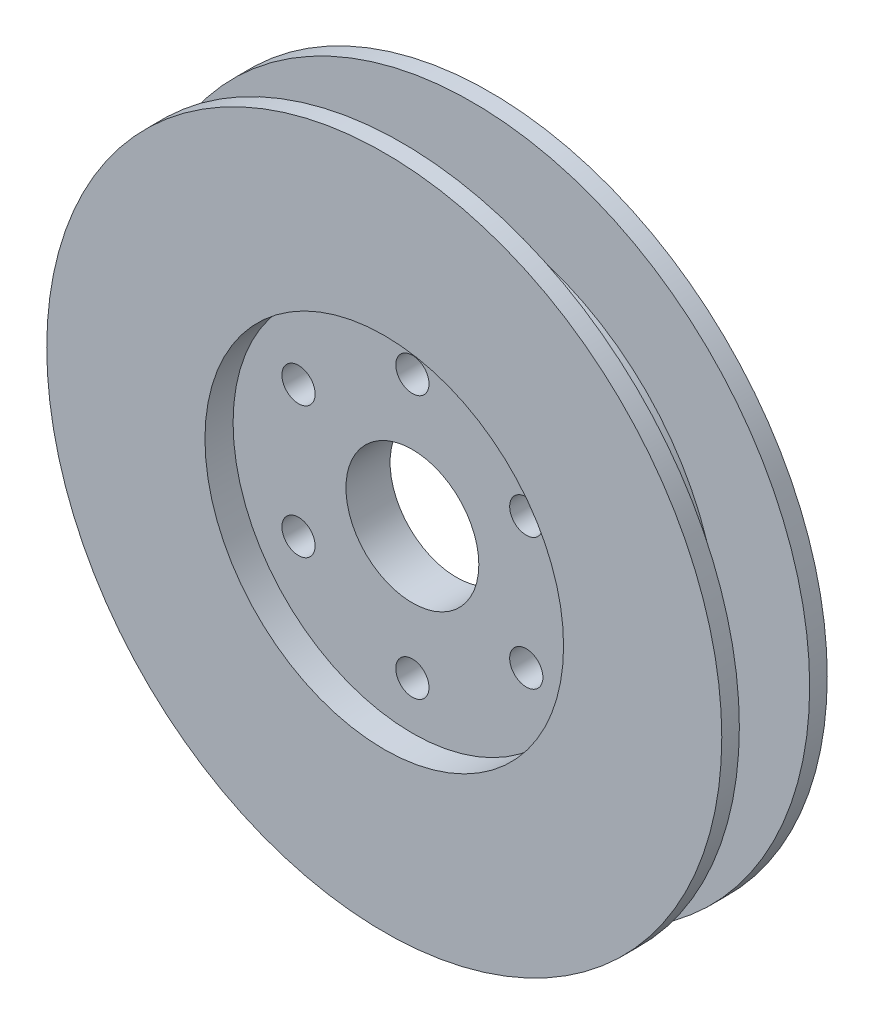
SolidWorks part; units mm, degrees
material "PE High Density Film"
ref_plane "Front Plane" through (0, 0, 0) normal (0, 0, 1) x (1, 0, 0)
ref_plane "Top Plane" through (0, 0, 0) normal (0, 1, 0) x (1, 0, 0)
ref_plane "Right Plane" through (0, 0, 0) normal (1, 0, 0) x (0, 0, -1)
sketch "Sketch1" plane through (0, 0, 0) normal (0, 0, 1) x (1, 0, 0)
  line L0 (0, 0) -> (0, 60.96)
  line L1 (-8.9803, 60.2949) -> (0, 51.3147)
  line L2 (0, 51.3147) -> (8.9803, 60.2949)
  line L3 (36.2849, 48.9849) -> (36.2849, 36.2849)
  line L4 (36.2849, 36.2849) -> (48.9849, 36.2849)
  line L5 (60.2949, 8.9803) -> (51.3147, 0)
  line L6 (51.3147, 0) -> (60.2949, -8.9803)
  line L7 (48.9849, -36.2849) -> (36.2849, -36.2849)
  line L8 (36.2849, -36.2849) -> (36.2849, -48.9849)
  line L9 (8.9803, -60.2949) -> (0, -51.3147)
  line L10 (0, -51.3147) -> (-8.9803, -60.2949)
  line L11 (-36.2849, -48.9849) -> (-36.2849, -36.2849)
  line L12 (-36.2849, -36.2849) -> (-48.9849, -36.2849)
  line L13 (-60.2949, -8.9803) -> (-51.3147, 0)
  line L14 (-51.3147, 0) -> (-60.2949, 8.9803)
  line L15 (-48.9849, 36.2849) -> (-36.2849, 36.2849)
  line L16 (-36.2849, 36.2849) -> (-36.2849, 48.9849)
  arc A0 (-60.2949, -8.9803) -> (-48.9849, -36.2849) centre (0, 0) ccw
  arc A1 (-48.9849, 36.2849) -> (-60.2949, 8.9803) centre (0, 0) ccw
  arc A2 (-36.2849, -48.9849) -> (-8.9803, -60.2949) centre (0, 0) ccw
  arc A3 (8.9803, -60.2949) -> (36.2849, -48.9849) centre (0, 0) ccw
  arc A4 (48.9849, -36.2849) -> (60.2949, -8.9803) centre (0, 0) ccw
  arc A5 (60.2949, 8.9803) -> (48.9849, 36.2849) centre (0, 0) ccw
  arc A6 (36.2849, 48.9849) -> (8.9803, 60.2949) centre (0, 0) ccw
  arc A7 (-8.9803, 60.2949) -> (-36.2849, 48.9849) centre (0, 0) ccw
  circle A8 centre (0, 0) radius 60.96
  point P30 (0, 0)
  dimension "D1" = 121.92
  dimension "D2" = 45
  dimension "D3" = 12.7
  dimension "D4" = 8
extrude "Boss-Extrude1" add sketch "Sketch1" along normal blind 19.05 contours L14 A8 L13 | L16 A8 L15 | L0 A8 L1 | L4 A8 L3 | L6 A8 L5 | L8 A8 L7 | L10 A8 L9 | L12 A8 L11 | L2 A8 L0 | L8 A3 L9 L10 A2 L11 L12 A0 L13 L14 A1 L15 L16 A7 L1 L2 A6 L3 L4 A5 L5 L6 A4 L7 region at (-3.0273, 57.5947, 0) region at (3.0273, 57.5947, 0) region at (-40.7256, 40.7256, 0) region at (40.7256, 40.7256, 0) region at (-57.5947, 0, 0) region at (57.5947, 0, 0) region at (-40.7256, -40.7256, 0) region at (40.7256, -40.7256, 0) region at (0, -57.5947, 0)
sketch "Sketch2" plane through (0, 0, 19.05) normal (0, 0, 1) x (1, 0, 0)
  circle A0 centre (0, 0) radius 12
  dimension "D1" = 24
extrude "Cut-Extrude1" cut sketch "Sketch2" against normal through all contours A0 region at (0, 0, 19.05)
sketch "Sketch3" plane through (0, 0, 19.05) normal (0, 0, 1) x (1, 0, 0)
  circle A0 centre (0, 0) radius 32.385
  dimension "D1" = 64.77
extrude "Cut-Extrude2" cut sketch "Sketch3" against normal blind 5.08
sketch "Sketch4" plane through (0, 0, 0) normal (0, 0, -1) x (-1, 0, 0)
  circle A0 centre (0, 0) radius 28.4
  dimension "D1" = 56.8
extrude "Cut-Extrude3" cut sketch "Sketch4" against normal blind 6
sketch "Sketch5" plane through (0, 0, 6) normal (0, 0, -1) x (-1, 0, 0)
  line L0 (0, 0) -> (0, 23.75) construction
  circle A0 centre (0, 0) radius 23.75 construction
  circle A1 centre (0, 23.75) radius 2.6
  circle A2 centre (20.5681, 11.875) radius 2.6
  circle A3 centre (20.5681, -11.875) radius 2.6
  circle A4 centre (0, -23.75) radius 2.6
  circle A5 centre (-20.5681, -11.875) radius 2.6
  circle A6 centre (-20.5681, 11.875) radius 2.6
  point P17 (0, 0)
  dimension "D1" = 47.5
  dimension "D2" = 5.2
  dimension "D3" = 6
hole_wizard "Ø6.0mm Dowel Hole1" positions "Sketch6" profile "Sketch8" hole size "Ø6.0" standard "ANSI Metric" end condition through all
sketch "Sketch6" plane through (0, 0, 6) normal (0, 0, -1) x (-1, 0, 0)
  point P0 (0, 23.75)
  point P3 (20.5681, 11.875)
  point P6 (20.5681, -11.875)
  point P9 (0, -23.75)
  point P13 (-20.5681, 11.875)
  point P16 (-20.5681, -11.875)
sketch "Sketch8" plane through (0, 23.75, 6) normal (1, 0, 0) x (0, 1, 0)
  line L0 (0, 0) -> (0, 13.05)
  line L1 (0, 13.05) -> (3, 13.05)
  line L2 (3, 13.05) -> (3, 0)
  line L5 (3, 0) -> (0, 0)
  line L11 (0, -6.35) -> (0, 107.95) construction
  dimension "Thru Hole Dia." = 6
  dimension "Thru Hole Depth" = 13.05
ref_plane "Plane1" through (0, 0, 9.525) normal (0, 0, 1) x (1, 0, 0)
sketch "Sketch11" plane through (0, 0, 9.525) normal (0, 0, 1) x (1, 0, 0)
  line L0 (0, 0) -> (0, 50.8) construction
  line L1 (0, 38.1) -> (-15.875, 38.1)
  line L2 (-15.875, 38.1) -> (-15.875, 63.5)
  line L3 (-15.875, 63.5) -> (15.875, 63.5)
  line L4 (15.875, 63.5) -> (15.875, 38.1)
  line L5 (15.875, 38.1) -> (0, 38.1)
  line L6 (0, 50.8) -> (-15.875, 50.8) construction
  line L7 (0, 0) -> (25.4, 0) construction
  dimension "D1" = 25.4
  dimension "D2" = 90
  dimension "D3" = 31.75
  dimension "D4" = 25.4
  dimension "D5" = 50.8
extrude "Cut-Extrude6" [suppressed] cut sketch "Sketch11" against normal mid plane 11.1125
sketch "Sketch12" plane through (0, 0, 0) normal (1, 0, 0) x (0, 0, -1)
  line L0 (0, 0) -> (-19.05, 0) construction
  line L1 (-9.525, 0) -> (-9.525, 63.5) construction
  line L2 (-19.05, 32.385) -> (-19.05, -32.385) construction
  line L3 (-3.175, 63.5) -> (-15.875, 63.5)
  line L4 (-15.875, 63.5) -> (-15.875, 50.8)
  line L6 (-15.875, 50.8) -> (-15.875, 44.45)
  line L7 (-15.875, 44.45) -> (-3.175, 44.45)
  line L8 (-3.175, 44.45) -> (-3.175, 50.8)
  line L10 (-3.175, 50.8) -> (-3.175, 63.5)
  dimension "D1" = 63.5
  dimension "D2" = 12.7
  dimension "D3" = 12.7
  dimension "D4" = 6.35
revolve "Cut-Revolve1" cut sketch "Sketch12" angle 360 about L0
